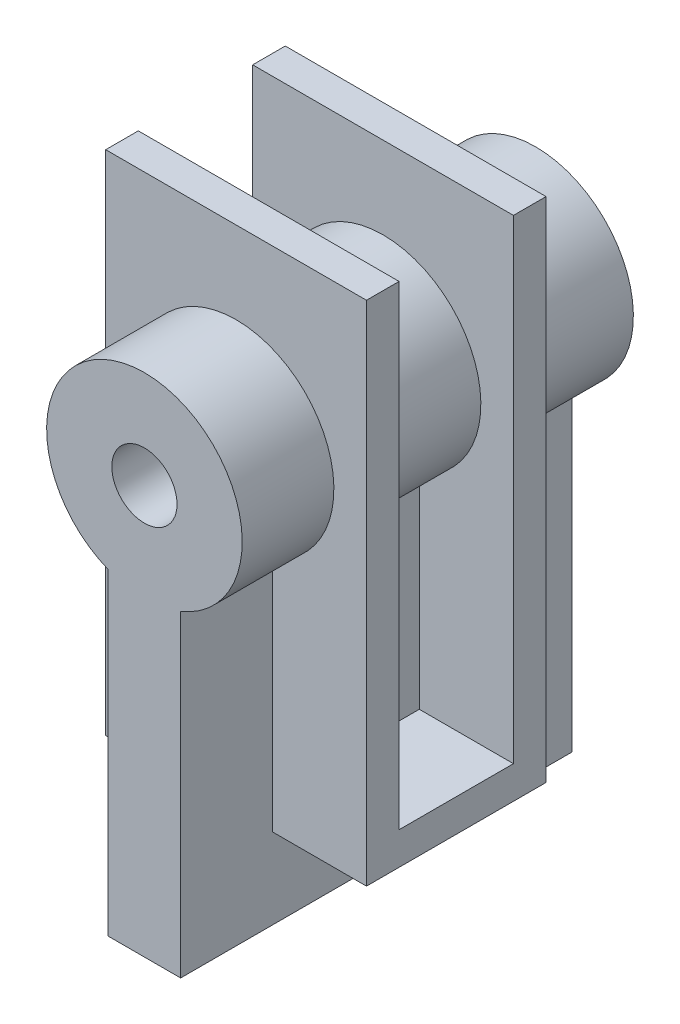
SolidWorks part; units mm, degrees
ref_plane "Спереди" through (0, 0, 0) normal (0, 0, 1) x (1, 0, 0)
ref_plane "Сверху" through (0, 0, 0) normal (0, 1, 0) x (1, 0, 0)
ref_plane "Справа" through (0, 0, 0) normal (1, 0, 0) x (0, 0, -1)
sketch "Эскиз1_fr" plane through (0, 0, 0) normal (0, 0, 1) x (1, 0, 0)
  line L2 (-5.5576, -13.9324) -> (-5.5576, -62.6423)
  line L3 (-5.5576, -62.6423) -> (5.5576, -62.6423)
  line L4 (5.5576, -13.9324) -> (5.5576, -62.6423)
  circle A0 centre (0, 0) radius 5
  arc A1 (5.5576, -13.9324) -> (-5.5576, -13.9324) centre (0, 0) ccw
  circle A3 centre (0, 0) radius 15 construction
  point P9 (14.3446, 4.3856)
  dimension "D1" = 10
  dimension "D2" = 30
sketch "Эскиз3" plane through (0, 0, 0) normal (1, 0, 0) x (0, 0, -1)
  line L0 (-58.3945, -50.2531) -> (-85.9381, -50.2531)
  line L1 (-85.9381, -50.2531) -> (-85.9381, 27.5805)
  line L2 (-58.3945, -50.2531) -> (-58.3945, 27.5805)
  line L3 (-80.9381, -45.2531) -> (-80.9381, 27.5805)
  line L4 (-63.3945, -45.2531) -> (-80.9381, -45.2531)
  line L5 (-63.3945, -45.2531) -> (-63.3945, 27.5805)
  line L6 (-85.9381, 27.5805) -> (-80.9381, 27.5805)
  line L7 (-63.3945, 27.5805) -> (-58.3945, 27.5805)
  point P3 (-72.1663, -50.2531)
extrude "Бобышка-Вытянуть5" add sketch "Эскиз1_fr" along normal blind 30 and the other way blind 30
extrude "Бобышка-Вытянуть6" add sketch "Эскиз3" along normal blind 20 and the other way blind 20 separate body
move or copy body "Тело-Переместить/Копировать1" bodies to move or copy 114 copy no translate (0, 0, -70)
